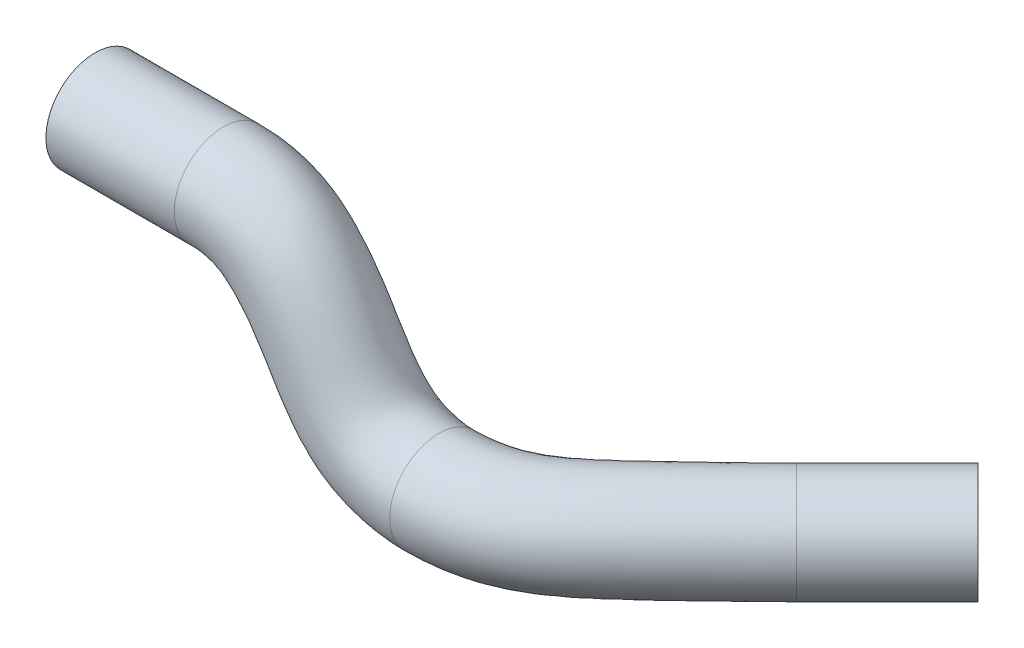
SolidWorks part; units mm, degrees
ref_plane "Front Plane" through (0, 0, 0) normal (0, 0, 1) x (1, 0, 0)
ref_plane "Top Plane" through (0, 0, 0) normal (0, 1, 0) x (1, 0, 0)
ref_plane "Right Plane" through (0, 0, 0) normal (1, 0, 0) x (0, 0, -1)
sketch "Sketch1" plane through (0, 0, 0) normal (0, 0, 1) x (1, 0, 0)
  line L0 (0, 0) -> (-25.2044, 0)
  line L1 (0, 0) -> (0, -30.988) construction
  line L2 (0, -30.988) -> (84.6607, -30.988) construction
  line L3 (0, -30.988) -> (42.3304, -30.988) construction
  spline S0 degree 3 poles (0, 0) (4.1894, 0) (12.5752, -2.1786) (21.4347, -15.494) (28.884, -28.8094) (39.2145, -30.988) (42.3304, -30.988) knots 0 0 0 0 0.190618 0.5 0.809382 1 1 1 1
  point P7 (21.1652, -30.988)
  point P9 (0, 0)
  point P11 (0, -15.494)
  dimension "D1" = 25.2044
  dimension "D2" = 30.988
  dimension "D3" = 84.6607
  dimension "D4" = 10.16
  dimension "D5" = 2.54
  dimension "D6" = 10.16
  dimension "D7" = 2.54
ref_plane "Plane1" through (0, -30.988, 0) normal (0, 1, 0) x (1, 0, 0)
sketch "Sketch2" plane through (0, -30.988, 0) normal (0, 1, 0) x (1, 0, 0)
  line L0 (84.6607, 0) -> (84.6607, 27.94) construction
  line L1 (0, 0) -> (84.6607, 0) construction
  line L2 (84.6607, 27.94) -> (102.483, 45.7622)
  line L3 (0, 0) -> (42.3304, 0) construction
  line L4 (42.3304, 0) -> (84.6607, 0) construction
  spline S0 degree 3 poles (84.6607, 27.94) (82.2898, 25.569) (76.5557, 20.1234) (66.8204, 10.7368) (55.8035, 1.2905) (46.0207, 0) (42.3304, 0) knots 0 0 0 0 0.192815 0.455013 0.785296 1 1 1 1
  point P8 (0, 0)
  point P10 (53.3649, 1.8064)
  point P12 (67.5192, 11.5796)
  dimension "D1" = 27.94
  dimension "D2" = 25.2044
  dimension "D3" = 45
  dimension "D4" = 6.985
ref_plane "Plane2" through (-25.2044, 0, 0) normal (1, 0, 0) x (0, 0, -1)
sketch "Sketch3" plane through (-25.2044, 0, 0) normal (1, 0, 0) x (0, 0, -1)
  circle A0 centre (0, 0) radius 7.112
  circle A1 centre (0, 0) radius 9.652
  dimension "D1" = 14.224
  dimension "D2" = 2.54
sweep "Sweep1" add profiles "Sketch3" path "Sketch1"
sketch "Sketch4" plane through (42.3304, 0, 0) normal (1, 0, 0) x (0, 0, -1)
  circle A0 centre (0, -30.988) radius 7.112
  circle A1 centre (0, -30.988) radius 9.652
  circle A2 centre (0, -30.988) radius 9.652
  dimension "D2" = 14.224
  dimension "D1" = 0
sweep "Sweep2" add profiles "Sketch4" path "Sketch2"
